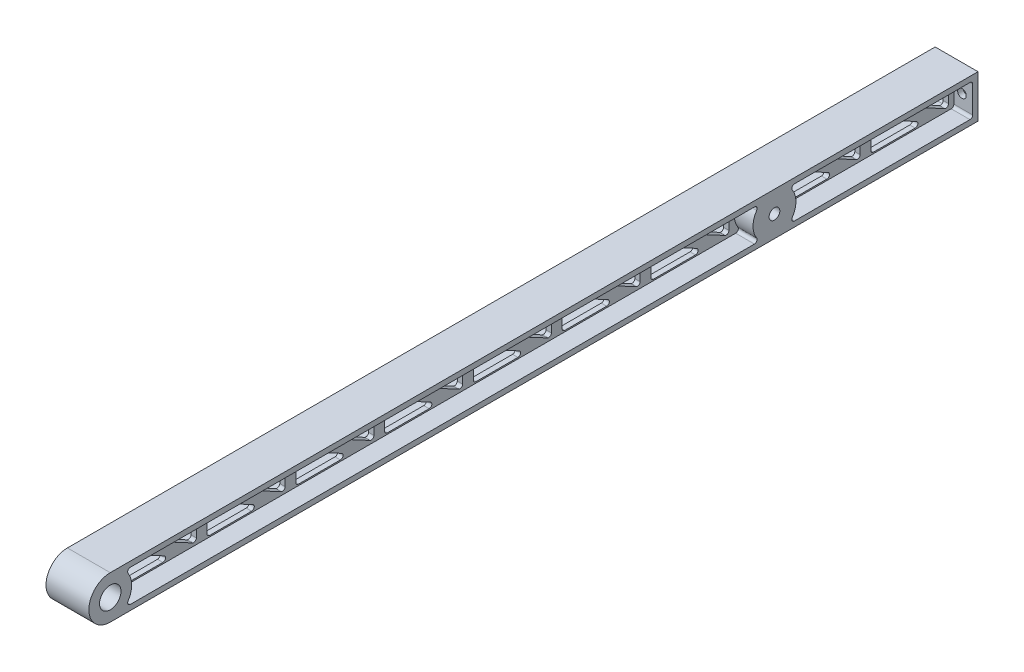
SolidWorks part; units mm, degrees
material "6061 Alloy"
ref_plane "Front Plane" through (0, 0, 0) normal (0, 0, 1) x (1, 0, 0)
ref_plane "Top Plane" through (0, 0, 0) normal (0, 1, 0) x (1, 0, 0)
ref_plane "Right Plane" through (0, 0, 0) normal (1, 0, 0) x (0, 0, -1)
sketch "Sketch1" plane through (0, 0, 0) normal (1, 0, 0) x (0, 0, -1)
  line L0 (0, 12.7) -> (514.35, 12.7)
  line L1 (0, -12.7) -> (514.35, -12.7)
  line L2 (514.35, 12.7) -> (514.35, 28.575) construction
  line L3 (514.35, 28.575) -> (520.7, 28.575) construction
  line L4 (520.7, 28.575) -> (520.7, -28.575) construction
  line L5 (520.7, -28.575) -> (514.35, -28.575) construction
  line L6 (514.35, -28.575) -> (514.35, -12.7) construction
  line L7 (514.35, 19.05) -> (558.8, 19.05) construction
  line L8 (558.8, 19.05) -> (558.8, -19.05) construction
  line L9 (558.8, -19.05) -> (514.35, -19.05) construction
  line L10 (514.35, 12.7) -> (514.35, -12.7)
  circle A0 centre (0, 0) radius 6.35
  arc A1 (0, -12.7) -> (0, 12.7) centre (0, 0) cw
  circle A4 centre (558.8, 0) radius 6.35 construction
  point P17 (520.7, 0)
  dimension "D1" = 12.7
  dimension "D2" = 12.7
  dimension "D6" = 38.1
  dimension "D3" = 6.35
  dimension "D4" = 57.15
  dimension "D7" = 558.8
  dimension "D8" = 25.4
  dimension "D9" = 38.1
extrude "Boss-Extrude1" add sketch "Sketch1" along normal blind 25.4
hole_wizard "1/4-20 Tapped Hole1" positions "Sketch3" profile "Sketch2" tap size "1/4-20" standard "ANSI Inch"
sketch "Sketch3" plane through (0, 0, -514.35) normal (0, 0, -1) x (-1, 0, 0)
  line L0 (0, 0) -> (-6.35, 0) construction
  line L2 (-6.35, 0) -> (-19.05, 0) construction
  line L3 (-19.05, 0) -> (-25.4, 0) construction
  line L5 (0, -12.7) -> (0, 12.7) construction
  line L6 (-25.4, -12.7) -> (-25.4, 12.7) construction
  point P13 (-6.35, 0)
  point P15 (-19.05, 0)
  dimension "D1" = 12.7
sketch "Sketch2" plane through (6.35, 0, -514.35) normal (1, 0, 0) x (0, 1, 0)
  line L0 (0, 0) -> (0, 18.0438)
  line L1 (0, 18.0438) -> (2.5527, 16.51)
  line L2 (2.5527, 16.51) -> (2.5527, 0)
  line L5 (2.5527, 0) -> (0, 0)
  line L10 (0, 18.0438) -> (-2.5527, 16.51) construction
  line L11 (0, -6.35) -> (0, 107.95) construction
  dimension "Tap Drill Dia." = 5.1054
  dimension "Tap Drill Depth" = 16.51
  dimension "Drill Angle" = 118
sketch "Sketch4" plane through (25.4, 0, 0) normal (1, 0, 0) x (0, 0, -1)
  line L0 (0, 0) -> (393.7, 0) construction
  circle A0 centre (393.7, 0) radius 3.175
  dimension "D1" = 6.35
  dimension "D2" = 393.7
extrude "Cut-Extrude1" cut sketch "Sketch4" against normal blind 38.1
sketch "Sketch19" plane through (25.4, 0, 0) normal (1, 0, 0) x (0, 0, -1)
  line L0 (0, 12.7) -> (0, 9.525)
  line L1 (0, -12.7) -> (0, -9.525)
  line L2 (0, 9.525) -> (514.35, 9.525)
  line L3 (514.35, -12.7) -> (514.35, 12.7) construction
  line L4 (514.35, -9.525) -> (0, -9.525)
  line L5 (514.35, 9.525) -> (511.175, 9.525)
  line L6 (511.175, 9.525) -> (511.175, -9.525)
  circle A0 centre (0, 0) radius 12.7
  circle A1 centre (393.7, 0) radius 12.7
  line M4 (514.35, -12.7) -> (514.35, 12.7)
  dimension "D1" = 25.4
  dimension "D2" = 25.4
  dimension "D3" = 3.175
  dimension "D4" = 3.175
  dimension "D5" = 3.175
extrude "Cut-Extrude2" cut sketch "Sketch19" against normal blind 11.1125 contours A1 L2 A0 L4 | A1 L4 L2 M4 region at (25.4, 0, -196.85) region at (25.4, 0, -458.1205)
sketch "Sketch21" plane through (14.2875, 0, 0) normal (1, 0, 0) x (0, 0, -1)
  line L0 (12.7, 0) -> (15.875, 0) construction
  line L1 (15.875, 8.7312) -> (15.875, -8.7312)
  line L2 (15.875, -8.7312) -> (48.6386, -8.7312)
  line L3 (48.6386, -8.7312) -> (15.875, 8.7312)
  line L4 (29.3756, 8.7312) -> (62.1393, -8.7312)
  line L5 (29.3756, 8.7312) -> (62.1393, 8.7312)
  line L6 (62.1393, 8.7312) -> (62.1393, -8.7312)
  line L7 (42.7708, -5.6038) -> (45.7575, 0) construction
  line L8 (68.4893, 8.7312) -> (68.4893, -8.7312)
  line L9 (68.4893, -8.7312) -> (101.2529, -8.7312)
  line L10 (101.2529, -8.7312) -> (68.4893, 8.7312)
  line L11 (81.9899, 8.7312) -> (114.7536, -8.7312)
  line L12 (81.9899, 8.7312) -> (114.7536, 8.7312)
  line L13 (114.7536, 8.7312) -> (114.7536, -8.7312)
  line L14 (65.3143, 0) -> (68.4893, 0) construction
  line L15 (95.385, -5.6038) -> (98.3717, 0) construction
  line L16 (121.1036, 8.7312) -> (121.1036, -8.7312)
  line L17 (121.1036, -8.7312) -> (153.8672, -8.7312)
  line L18 (153.8672, -8.7312) -> (121.1036, 8.7312)
  line L19 (134.6042, 8.7312) -> (167.3679, -8.7312)
  line L20 (134.6042, 8.7312) -> (167.3679, 8.7312)
  line L21 (167.3679, 8.7312) -> (167.3679, -8.7312)
  line L22 (117.9286, 0) -> (121.1036, 0) construction
  line L23 (147.9993, -5.6038) -> (150.986, 0) construction
  line L24 (173.7179, 8.7312) -> (173.7179, -8.7312)
  line L25 (173.7179, -8.7312) -> (206.4815, -8.7312)
  line L26 (206.4815, -8.7312) -> (173.7179, 8.7312)
  line L27 (187.2185, 8.7312) -> (219.9821, -8.7312)
  line L28 (187.2185, 8.7312) -> (219.9821, 8.7312)
  line L29 (219.9821, 8.7312) -> (219.9821, -8.7312)
  line L30 (170.5429, 0) -> (173.7179, 0) construction
  line L31 (200.6136, -5.6038) -> (203.6003, 0) construction
  line L32 (226.3321, 8.7312) -> (226.3321, -8.7312)
  line L33 (226.3321, -8.7312) -> (259.0958, -8.7312)
  line L34 (259.0958, -8.7312) -> (226.3321, 8.7312)
  line L35 (239.8328, 8.7312) -> (272.5964, -8.7312)
  line L36 (239.8328, 8.7312) -> (272.5964, 8.7312)
  line L37 (272.5964, 8.7312) -> (272.5964, -8.7312)
  line L38 (223.1571, 0) -> (226.3321, 0) construction
  line L39 (253.2279, -5.6038) -> (256.2146, 0) construction
  line L40 (278.9464, 8.7312) -> (278.9464, -8.7312)
  line L41 (278.9464, -8.7312) -> (311.7101, -8.7312)
  line L42 (311.7101, -8.7312) -> (278.9464, 8.7312)
  line L43 (292.4471, 8.7312) -> (325.2107, -8.7312)
  line L44 (292.4471, 8.7312) -> (325.2107, 8.7312)
  line L45 (325.2107, 8.7312) -> (325.2107, -8.7312)
  line L46 (275.7714, 0) -> (278.9464, 0) construction
  line L47 (305.8422, -5.6038) -> (308.8289, 0) construction
  line L48 (331.5607, 8.7312) -> (331.5607, -8.7312)
  line L49 (331.5607, -8.7312) -> (364.3244, -8.7312)
  line L50 (364.3244, -8.7312) -> (331.5607, 8.7312)
  line L51 (345.0614, 8.7312) -> (377.825, -8.7312)
  line L52 (345.0614, 8.7312) -> (377.825, 8.7312)
  line L53 (377.825, 8.7312) -> (377.825, -8.7312)
  line L54 (328.3857, 0) -> (331.5607, 0) construction
  line L55 (358.4565, -5.6038) -> (361.4432, 0) construction
  line L80 (377.825, 0) -> (381, 0) construction
  line L104 (15.875, 8.7312) -> (68.4893, 8.7312) construction
  line L105 (406.4, 0) -> (409.575, 0)
  line L106 (409.575, 8.7313) -> (409.575, -8.7312)
  line L107 (409.575, -8.7312) -> (442.1669, -8.7313)
  line L108 (442.1669, -8.7313) -> (409.575, 8.7313)
  line L109 (423.0206, 8.7312) -> (455.6125, -8.7313)
  line L110 (455.6125, -8.7313) -> (455.6125, 8.7312)
  line L111 (455.6125, 8.7312) -> (423.0206, 8.7312)
  line L112 (425.871, 0) -> (428.8699, 5.5972)
  line L113 (458.7875, 0) -> (461.9625, 0)
  line L114 (461.9625, 8.7312) -> (461.9625, -8.7313)
  line L115 (461.9625, -8.7313) -> (494.5544, -8.7313)
  line L116 (494.5544, -8.7313) -> (461.9625, 8.7312)
  line L117 (475.4081, 8.7312) -> (508, -8.7313)
  line L118 (508, -8.7313) -> (508, 8.7312)
  line L119 (508, 8.7312) -> (475.4081, 8.7312)
  line L120 (478.2585, 0) -> (481.2574, 5.5972)
  line L130 (511.175, 0) -> (508, 0)
  line L131 (511.175, 9.525) -> (511.175, -9.525) construction
  arc A0 (8.4003, -9.525) -> (8.4003, 9.525) centre (0, 0) ccw construction
  arc A1 (385.2997, 9.525) -> (385.2997, -9.525) centre (393.7, 0) ccw construction
  arc A2 (402.1003, -9.525) -> (402.1003, 9.525) centre (393.7, 0) ccw construction
  dimension "D1" = 3.175
  dimension "D2" = 17.4625
  dimension "D3" = 6.35
  dimension "D4" = 7
  dimension "D5" = 6.35
  dimension "D6" = 3.175
  dimension "D7" = 17.4625
  dimension "D8" = 6.35
  dimension "D11" = 6.35
  dimension "D12" = 3.175
  dimension "D13" = 3.175
  dimension "D9" = 2
extrude "Cut-Extrude3" cut sketch "Sketch21" against normal through all contours L2 L3 L1 | L6 L5 L4 | L9 L10 L8 | L13 L12 L11 | L17 L18 L16 | L21 L20 L19 | L25 L26 L24 | L29 L28 L27 | L33 L34 L32 | L37 L36 L35 | L41 L42 L40 | L45 L44 L43 | L49 L50 L48 | L53 L52 L51 | L107 L108 L106 | L110 L111 L109 | L115 L116 L114 | L118 L119 L117 region at (14.2875, -2.9104, -26.7962) region at (14.2875, 2.9104, -51.2181) region at (14.2875, -2.9104, -79.4105) region at (14.2875, 2.9104, -103.8324) region at (14.2875, -2.9104, -132.0248) region at (14.2875, 2.9104, -156.4466) region at (14.2875, -2.9104, -184.6391) region at (14.2875, 2.9104, -209.0609) region at (14.2875, -2.9104, -237.2534) region at (14.2875, 2.9104, -261.6752) region at (14.2875, -2.9104, -289.8676) region at (14.2875, 2.9104, -314.2895) region at (14.2875, -2.9104, -342.4819) region at (14.2875, 2.9104, -366.9038) region at (14.2875, -2.9104, -420.439) region at (14.2875, 2.9104, -444.7485) region at (14.2875, -2.9104, -472.8265) region at (14.2875, 2.9104, -497.136)
ref_plane "half arm" through (12.7, 0, 0) normal (-1, 0, 0) x (0, 0, 1)
mirror "Mirror2" about plane through (12.7, 0, 0) normal (-1, 0, 0) of "Cut-Extrude2"
fillet "Fillet2" radius 1.5875 70 edges at (12.7, 8.7312, -15.875) (12.7, -8.7313, -48.6386) (12.7, 8.7312, -62.1393) (12.7, -8.7312, -62.1393) (12.7, 8.7313, -29.3756) (12.7, -8.7312, -121.1036) (12.7, 8.7313, -121.1036) (12.7, -8.7313, -153.8672) (12.7, 8.7312, -167.3679) (12.7, -8.7313, -167.3679) (12.7, 8.7312, -134.6042) (12.7, -8.7312, -226.3321) (12.7, 8.7312, -226.3321) (12.7, -8.7313, -259.0958) (12.7, 8.7312, -272.5964) (12.7, -8.7312, -272.5964) (12.7, 8.7313, -239.8328) (12.7, -8.7312, -331.5607) (12.7, 8.7312, -331.5607) (12.7, -8.7312, -364.3244) (12.7, 8.7312, -377.825) (12.7, -8.7312, -377.825) (12.7, 8.7312, -345.0614) (12.7, 8.7312, -325.2107) (12.7, -8.7312, -325.2107) (12.7, 8.7313, -292.4471) (12.7, -8.7312, -278.9464) (12.7, 8.7312, -278.9464) (12.7, -8.7312, -311.7101) (12.7, 8.7312, -219.9821) (12.7, -8.7312, -219.9821) (12.7, 8.7312, -187.2185) (12.7, -8.7312, -173.7179) (12.7, 8.7312, -173.7179) (12.7, -8.7312, -206.4815) (12.7, 8.7312, -114.7536) (12.7, -8.7313, -114.7536) (12.7, 8.7312, -81.9899) (12.7, -8.7312, -68.4893) (12.7, 8.7312, -68.4893) (12.7, -8.7313, -101.2529) (12.7, -8.7312, -15.875) (5.5562, -9.525, -385.2997) (5.5562, 9.525, -8.4003) (5.5562, 9.525, -385.2997) (5.5562, 9.525, -402.1003) (5.5562, 9.525, -511.175) (5.5562, -9.525, -511.175) (5.5562, -9.525, -402.1003) (5.5562, -9.525, -8.4003) (19.8438, -9.525, -402.1003) (19.8438, -9.525, -511.175) (19.8438, 9.525, -511.175) (19.8438, 9.525, -402.1003) (19.8438, 9.525, -385.2997) (19.8438, 9.525, -8.4003) (19.8438, -9.525, -385.2997) (19.8438, -9.525, -8.4003) (12.7, 8.7313, -409.575) (12.7, -8.7313, -442.1669) (12.7, -8.7313, -461.9625) (12.7, 8.7312, -461.9625) (12.7, -8.7313, -494.5544) (12.7, -8.7313, -508) (12.7, 8.7312, -475.4081) (12.7, 8.7312, -508) (12.7, -8.7313, -455.6125) (12.7, 8.7312, -423.0206) (12.7, 8.7312, -455.6125) (12.7, -8.7312, -409.575)
